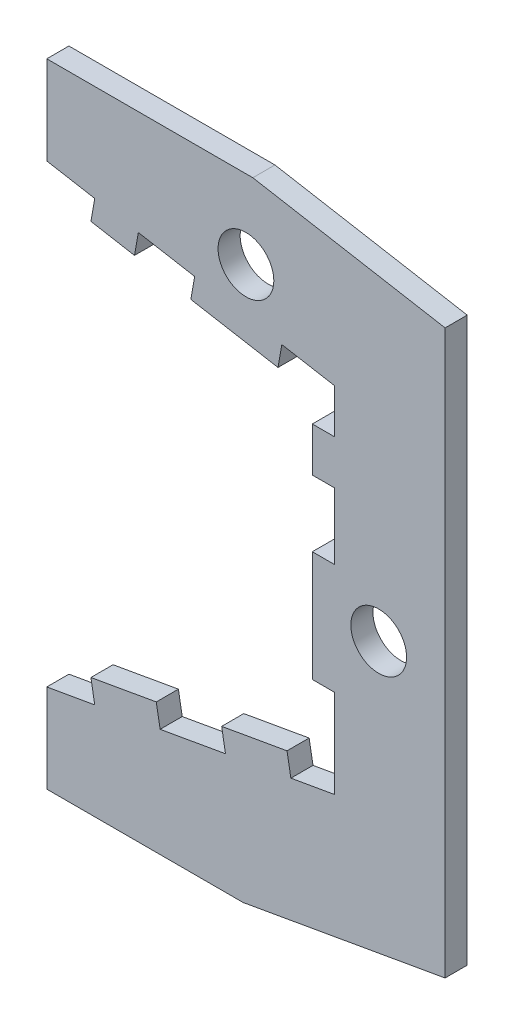
SolidWorks part; units mm, degrees
material "Balsa"
ref_plane "Plan de face" through (0, 0, 0) normal (0, 0, 1) x (1, 0, 0)
ref_plane "Plan de dessus" through (0, 0, 0) normal (0, 1, 0) x (1, 0, 0)
ref_plane "Plan de droite" through (0, 0, 0) normal (1, 0, 0) x (0, 0, -1)
sketch "Esquisse1" plane through (0, 0, 0) normal (0, 0, 1) x (1, 0, 0)
  line L0 (-65, 51.4613) -> (0, 40)
  line L1 (0, 40) -> (0, -40)
  line L2 (-65, -51.4613) -> (0, -40)
  line L3 (-18.4444, 71.4613) -> (-65, 71.4613)
  line L4 (-65, -51.4613) -> (-65, -71.4613)
  line L5 (-20.6259, -71.4613) -> (25, -63.4162)
  line L6 (25, -63.4162) -> (25, 63.8008)
  line L7 (25, 63.8008) -> (-18.4444, 71.4613)
  line L8 (-65, 71.4613) -> (-65, 51.4613)
  line L9 (-18.4444, 71.4613) -> (-20, 53.6808) construction
  line L10 (-65, -71.4613) -> (-20.6259, -71.4613)
  line L11 (0, 0) -> (-84.8855, 0) construction
  circle A0 centre (-20, 53.6808) radius 6.3
  circle A1 centre (10, -5) radius 6.3
  point P4 (-30.4766, 71.4613)
  point P13 (-6.595, 69.3719)
  point P15 (-65, -71.4613)
  dimension "D1" = 12.6
  dimension "D13" = 12.6
  dimension "D2" = 10
  dimension "D3" = 20
  dimension "D4" = 80
  dimension "D5" = 65
  dimension "D6" = 100
  dimension "D7" = 100
  dimension "D8" = 20
  dimension "D9" = 27.4016
  dimension "D10" = 90
  dimension "D11" = 10
  dimension "D12" = 35
  dimension "D14" = 100
extrude "Boss.-Extru.1" add sketch "Esquisse1" along normal blind 5
sketch "Esquisse4" plane through (0, 0, 5) normal (0, 0, 1) x (1, 0, 0)
  line L0 (0, 40) -> (0, -40) construction
  line L1 (0, 5) -> (-5, 5)
  line L2 (0, 5) -> (0, -20)
  line L3 (0, -20) -> (-5, -20)
  line L4 (-5, 5) -> (-5, -20)
  line L5 (-11.8884, 42.0962) -> (-31.5846, 45.5692)
  line L6 (-11.8884, 42.0962) -> (-12.7566, 37.1722)
  line L7 (-31.5846, 45.5692) -> (-32.4528, 40.6452)
  line L8 (-12.7566, 37.1722) -> (-32.4528, 40.6452)
  line L9 (-65, 51.4613) -> (0, 40) construction
  line L10 (-9.8481, -41.7365) -> (-24.6202, -44.3412)
  line L11 (0, 30) -> (-5, 30)
  line L12 (0, 30) -> (0, 20)
  line L13 (0, 20) -> (-5, 20)
  line L14 (-5, 30) -> (-5, 20)
  line L15 (-9.8481, -41.7365) -> (-10.7163, -36.8124)
  line L16 (-24.6202, -44.3412) -> (-25.4884, -39.4172)
  line L17 (-10.7163, -36.8124) -> (-25.4884, -39.4172)
  line L18 (0, -40) -> (-65, -51.4613) construction
  line L19 (-54.1644, -49.5506) -> (-39.3923, -46.9459)
  line L20 (-54.1644, -49.5506) -> (-55.0327, -44.6266)
  line L21 (-39.3923, -46.9459) -> (-40.2606, -42.0219)
  line L22 (-55.0327, -44.6266) -> (-40.2606, -42.0219)
  line L23 (-44.3163, 47.8142) -> (-54.1644, 49.5506)
  line L24 (-44.3163, 47.8142) -> (-45.1846, 42.8901)
  line L25 (-54.1644, 49.5506) -> (-55.0327, 44.6266)
  line L26 (-45.1846, 42.8901) -> (-55.0327, 44.6266)
  circle A0 centre (10, -5) radius 6.3 construction
  circle A1 centre (-20, 53.6808) radius 6.3 construction
  dimension "D1" = 10
  dimension "D2" = 25
  dimension "D3" = 10
  dimension "D4" = 20
  dimension "D5" = 5
  dimension "D6" = 5
  dimension "D7" = 15
  dimension "D8" = 10
  dimension "D9" = 10
  dimension "D10" = 15
  dimension "D11" = 15
  dimension "D12" = 15
  dimension "D13" = 5
  dimension "D14" = 55
  dimension "D15" = 10
extrude "Boss.-Extru.2" add sketch "Esquisse4" against normal blind 5
